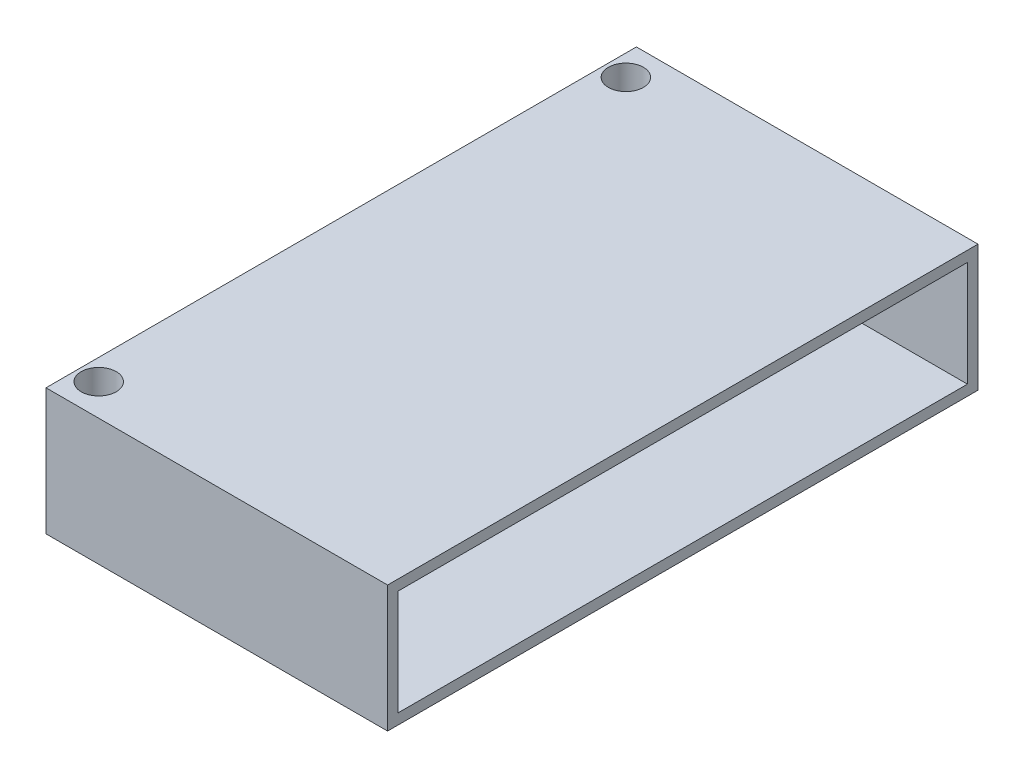
SolidWorks part; units mm, degrees
ref_plane "Front Plane" through (0, 0, 0) normal (0, 0, 1) x (1, 0, 0)
ref_plane "Top Plane" through (0, 0, 0) normal (0, 1, 0) x (1, 0, 0)
ref_plane "Right Plane" through (0, 0, 0) normal (1, 0, 0) x (0, 0, -1)
sketch "Sketch1" plane through (0, 0, 0) normal (0, 1, 0) x (1, 0, 0)
  line L0 (0, 140) -> (-70, 140)
  line L2 (0, 0) -> (0, 140)
  line L5 (0, 140) -> (-80, 140)
  line L6 (0, 140) -> (0, 0)
  line L7 (0, 0) -> (-80, 0)
  line L8 (-80, 140) -> (-80, 0)
  line L9 (-70, 140) -> (-70, 0)
  line L10 (-70, 0) -> (-80, 0)
  line L11 (0, 140) -> (1, 140)
  line L12 (-80, 0) -> (-80, 7.5)
  line L13 (1, 140) -> (1, 0)
  line L14 (1, 0) -> (0, 0)
  circle A0 centre (-75, 7.5) radius 2.5
  circle A1 centre (-75, 132.5) radius 2.5
  dimension "D2" = 140
  dimension "D3" = 80
  dimension "D4" = 70
extrude "Boss-Extrude2" add sketch "Sketch1" along normal blind 30 contours L0 L9 L7 L2 | L9 L5 L8 L7 A0 A1 | L14 L13 L11 L2 | A0 | A1 region at (-35, 0, -70) region at (0.5, 0, -70) region at (-75, 0, -70)
sketch "Sketch3" plane through (0, 30, 0) normal (0, 1, 0) x (1, 0, 0)
  line L0 (-80, 0) -> (-80, 7.5)
  line L1 (-80, 140) -> (-80, 0) construction
  line L2 (-80, 7.5) -> (-75, 7.5)
  line L3 (-80, 140) -> (-80, 132.5)
  line L4 (-80, 132.5) -> (-75, 132.5)
  circle A0 centre (-75, 7.5) radius 4.15
  circle A1 centre (-75, 132.5) radius 4.15
  dimension "D2" = 5
  dimension "D3" = 8.3
  dimension "D4" = 8.3
  dimension "D1" = 5
extrude "Cut-Extrude2" cut sketch "Sketch3" against normal blind 7 contours A1 | A0 region at (-75, 30, -3.4674) region at (-75, 30, -128.4674)
shell "Shell1" thickness 2.5 removed face at (1, 15, -70)
